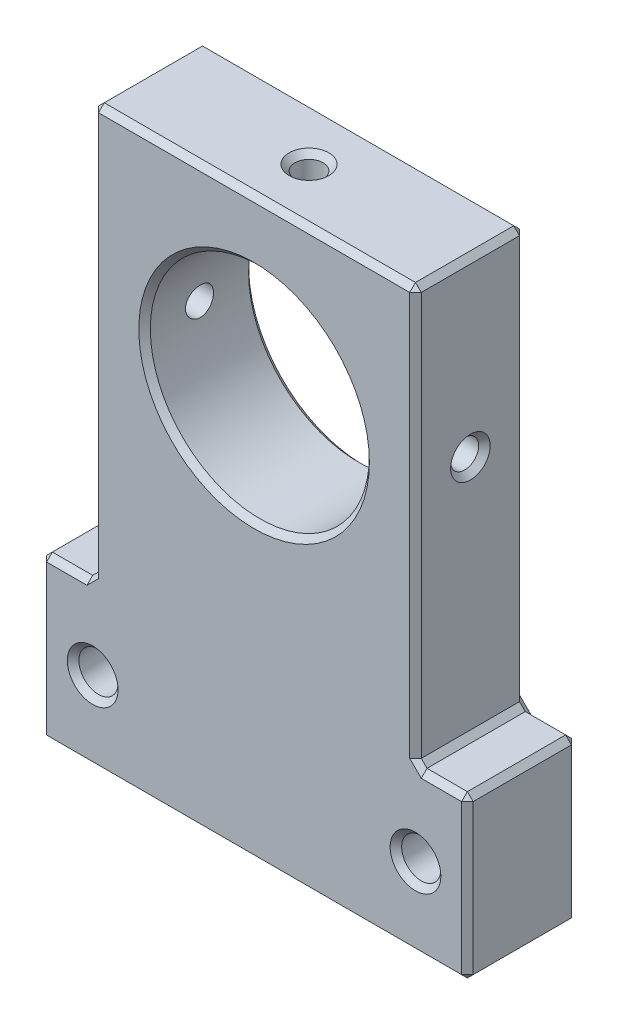
SolidWorks part; units mm, degrees
ref_plane "Front Plane" through (0, 0, 0) normal (0, 0, 1) x (1, 0, 0)
ref_plane "Top Plane" through (0, 0, 0) normal (0, 1, 0) x (1, 0, 0)
ref_plane "Right Plane" through (0, 0, 0) normal (1, 0, 0) x (0, 0, -1)
sketch "Sketch1" plane through (0, 0, 0) normal (0, 0, 1) x (-1, 0, 0)
  line L0 (-37, -50) -> (-37, 0)
  line L1 (-37, 0) -> (0, 0)
  line L2 (0, 0) -> (0, -50)
  line L3 (0, -50) -> (-37, -50)
  line L4 (-37, -50) -> (-36.8909, -50.0061)
  line L5 (-32.5, -50) -> (-32.5, -14)
  line L6 (-32.5, -14) -> (-37, -14)
  line L7 (0, -14) -> (-4.5, -14)
  line L8 (-4.5, -14) -> (-4.5, -50)
  circle A0 centre (-18.5, -35) radius 9.5
  circle A2 centre (-32.5, -7) radius 1.7
  circle A3 centre (-4.5, -7) radius 1.7
  dimension "D3" = 3.4
  dimension "D6" = 3.4
  dimension "D9" = 19
  dimension "D1" = 50
  dimension "D2" = 37
  dimension "D4" = 28
  dimension "D5" = 7
  dimension "D7" = 7
  dimension "D8" = 4.5
  dimension "D10" = 35
  dimension "D11" = 18.5
  dimension "D12" = 4.5
  dimension "D13" = 4.5
  dimension "D14" = 14
extrude "Boss-Extrude1" add sketch "Sketch1" along normal blind 9.525 contours L3 L2 L1 L0 A3 A2 A0 region at (18.5, 21.0987, 0)
sketch "Sketch2" plane through (0, 0, 0) normal (0, 0, -1) x (-1, 0, 0)
  circle A0 centre (-32.5, 7) radius 3.25
  circle A1 centre (-4.5, 7) radius 3.25
  dimension "D1" = 6.5
  dimension "D2" = 6.5
extrude "Cut-Extrude1" cut sketch "Sketch2" against normal blind 5.5
sketch "Sketch3" plane through (4.5, 0, 0) normal (-1, 0, 0) x (0, 0, 1)
  line L0 (9.525, 0) -> (0, 0) construction
  line L1 (0, 14) -> (0, 50) construction
  circle A0 centre (4.7625, 35) radius 1.2195
  dimension "D3" = 2.439
  dimension "D1" = 35
  dimension "D2" = 4.7625
extrude "Cut-Extrude2" cut sketch "Sketch3" against normal through all
sketch "Sketch4" plane through (0, 50, 0) normal (0, 1, 0) x (1, 0, 0)
  line L0 (4.5, -9.525) -> (32.5, -9.525) construction
  line L1 (4.5, -9.525) -> (4.5, 0) construction
  circle A0 centre (18.5, -4.7625) radius 1.2195
  dimension "D3" = 2.439
  dimension "D1" = 4.7625
  dimension "D2" = 14
extrude "Cut-Extrude3" cut sketch "Sketch4" against normal up to surface (5.5 mm away) up to face at (9.0038, 35.2692, 3.5731)
chamfer "Chamfer1" distance 0.5 angle 45 26 edges at (18.5, 0, 9.525) (37, 0, 4.7625) (37, 7, 9.525) (34.75, 14, 9.525) (37, 14, 4.7625) (32.5, 32, 9.525) (32.5, 14, 4.7625) (32.5, 50, 4.7625) (18.5, 50, 9.525) (4.5, 50, 4.7625) (4.5, 32, 9.525) (2.25, 14, 9.525) (4.5, 14, 4.7625) (0, 7, 9.525) (0, 0, 4.7625) (0, 14, 4.7625) (0, 7, 0) (2.25, 14, 0) (4.5, 32, 0) (18.5, 50, 0) (32.5, 32, 0) (34.75, 14, 0) (37, 7, 0) (18.5, 0, 0) (29.25, 7, 0) (1.25, 7, 0)
chamfer "Chamfer2" distance 0.5 angle 45 4 edges at (18.5, 50, 5.982) (4.5, 33.7805, 4.7625) (28, 35, 9.525) (28, 35, 0)
chamfer "Chamfer3" distance 0.5 angle 45 1 edges at (32.5, 35, 3.543)
chamfer "Chamfer4" distance 0.5 angle 45 2 edges at (6.2, 7, 9.525) (34.2, 7, 9.525)
